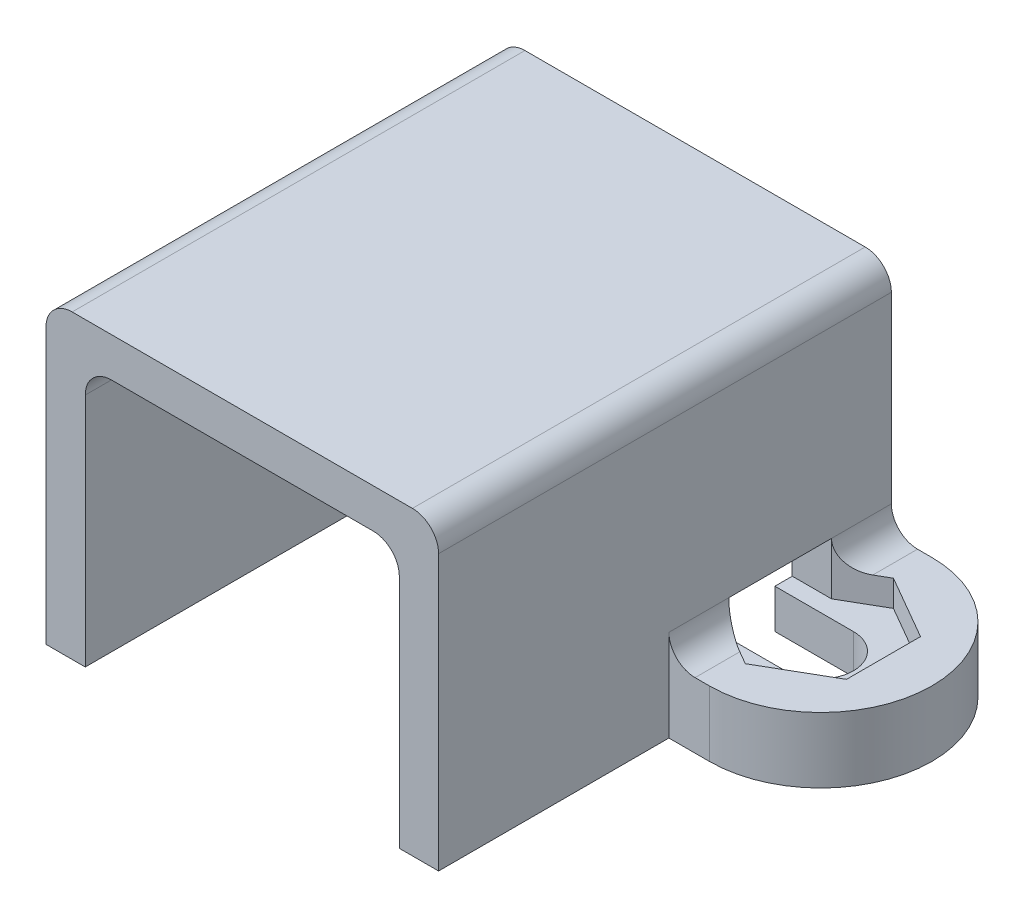
SolidWorks part; units mm, degrees
ref_plane "Front Plane" through (0, 0, 0) normal (0, 0, 1) x (1, 0, 0)
ref_plane "Top Plane" through (0, 0, 0) normal (0, 1, 0) x (1, 0, 0)
ref_plane "Right Plane" through (0, 0, 0) normal (1, 0, 0) x (0, 0, -1)
sketch "Sketch1" plane through (0, 0, 0) normal (0, 0, 1) x (1, 0, 0)
  line L0 (6, 0) -> (7.5, 0)
  line L1 (-7.5, 0) -> (-6, 0)
  line L2 (-7.5, 0) -> (-7.5, 11.5)
  line L3 (-7.5, 11.5) -> (7.5, 11.5)
  line L4 (7.5, 0) -> (7.5, 11.5)
  line L5 (6, 10) -> (-6, 10)
  line L6 (6, 10) -> (6, 0)
  line L8 (-6, 10) -> (-6, 0)
  point P4 (0, 10)
  point P5 (0, 11.5)
  dimension "D1" = 15
  dimension "D2" = 11.5
  dimension "D3" = 10
  dimension "D4" = 12
extrude "Boss-Extrude1" add sketch "Sketch1" along normal blind 17.3
sketch "Sketch2" plane through (0, 0, 0) normal (0, -1, 0) x (1, 0, 0)
  line L0 (-7.5, 0) -> (-9.05, 0)
  line L1 (-9.05, 8.5) -> (-7.5, 8.5)
  line L2 (-7.5, 17.3) -> (-7.5, 0) construction
  line L3 (-7.5, 8.5) -> (-7.5, 0)
  line L4 (7.5, 0) -> (9.05, 0)
  line L5 (9.05, 8.5) -> (7.5, 8.5)
  line L6 (7.5, 17.3) -> (7.5, 0) construction
  line L7 (7.5, 8.5) -> (7.5, 0)
  line L8 (0, 0) -> (0, 17.3) construction
  line L9 (-6, 17.3) -> (6, 17.3) construction
  arc A0 (-9.05, 0) -> (-9.05, 8.5) centre (-9.05, 4.25) cw
  arc A1 (9.05, 0) -> (9.05, 8.5) centre (9.05, 4.25) ccw
  dimension "D1" = 8.5
  dimension "D2" = 18.1
extrude "Boss-Extrude2" add sketch "Sketch2" against normal blind 2.5
sketch "Sketch3" plane through (0, 2.5, 0) normal (0, 1, 0) x (1, 0, 0)
  line L0 (6, -2.95) -> (9, -2.95)
  line L1 (0, 0) -> (0, -17.3) construction
  line L2 (9, -5.55) -> (6, -5.55)
  line L4 (-6, -2.95) -> (-9, -2.95)
  line L5 (7.5, -17.3) -> (-7.5, -17.3) construction
  line L6 (-9, -5.55) -> (-6, -5.55)
  line L8 (-6, -17.3) -> (-6, 0) construction
  line L9 (-6, -5.55) -> (-6, -2.95)
  line L10 (6, -17.3) -> (6, 0) construction
  line L11 (6, -5.55) -> (6, -2.95)
  arc A0 (9, -2.95) -> (9, -5.55) centre (9, -4.25) cw
  arc A1 (-9, -2.95) -> (-9, -5.55) centre (-9, -4.25) ccw
  arc A2 (9.05, -8.5) -> (9.05, 0) centre (9.05, -4.25) ccw construction
  point P17 (13.3, -4.25)
  dimension "D2" = 1.3
  dimension "D1" = 18
extrude "Cut-Extrude1" cut sketch "Sketch3" against normal up to surface (2.5 mm away) up to face at (8.225, 0, 8.6)
sketch "Sketch4" plane through (0, 2.5, 0) normal (0, 1, 0) x (1, 0, 0)
  line L0 (7.5, -17.3) -> (7.5, 0) construction
  line L1 (9, -1.421) -> (7.5, -2.287)
  line L3 (7.5, -6.213) -> (9, -7.079)
  line L4 (9, -7.079) -> (11.45, -5.6645)
  line L5 (11.45, -5.6645) -> (11.45, -2.8355)
  line L6 (11.45, -2.8355) -> (9, -1.421)
  line L14 (7.5, -2.287) -> (6, -2.287)
  line L15 (6, -2.287) -> (6, -6.213)
  line L16 (6, -6.213) -> (7.5, -6.213)
  line L17 (6, -17.3) -> (6, -5.55) construction
  line L18 (6.55, -4.25) -> (6.55, -5.6501) [skipped]
  line L20 (0, 0) -> (0, -17.3) construction
  line L21 (7.5, 0) -> (-7.5, 0) construction
  line L22 (7.5, -17.3) -> (-7.5, -17.3) construction
  line L24 (-6, -6.213) -> (-7.5, -6.213)
  line L25 (-6, -2.287) -> (-6, -6.213)
  line L26 (-7.5, -2.287) -> (-6, -2.287)
  line L28 (-11.45, -2.8355) -> (-9, -1.421)
  line L29 (-11.45, -5.6645) -> (-11.45, -2.8355)
  line L30 (-9, -7.079) -> (-11.45, -5.6645)
  line L31 (-7.5, -6.213) -> (-9, -7.079)
  line L32 (-9, -1.421) -> (-7.5, -2.287)
  circle A0 centre (9, -4.25) radius 2.45 construction
  circle A1 centre (-9, -4.25) radius 2.45 construction
  arc A2 (9, -5.55) -> (9, -2.95) centre (9, -4.25) ccw construction
  dimension "D1" = 4.9
extrude "Cut-Extrude2" cut sketch "Sketch4" against normal blind 1 and the other way blind 1
fillet "Fillet1" radius 1 6 edges at (-7.5, 2.5, 7.3565) (-7.5, 2.5, 1.1435) (7.5, 2.5, 1.1435) (7.5, 2.5, 7.3565) (-6, 10, 8.65) (6, 10, 8.65)
fillet "Fillet2" radius 1 2 edges at (7.5, 11.5, 8.65) (-7.5, 11.5, 8.65)
